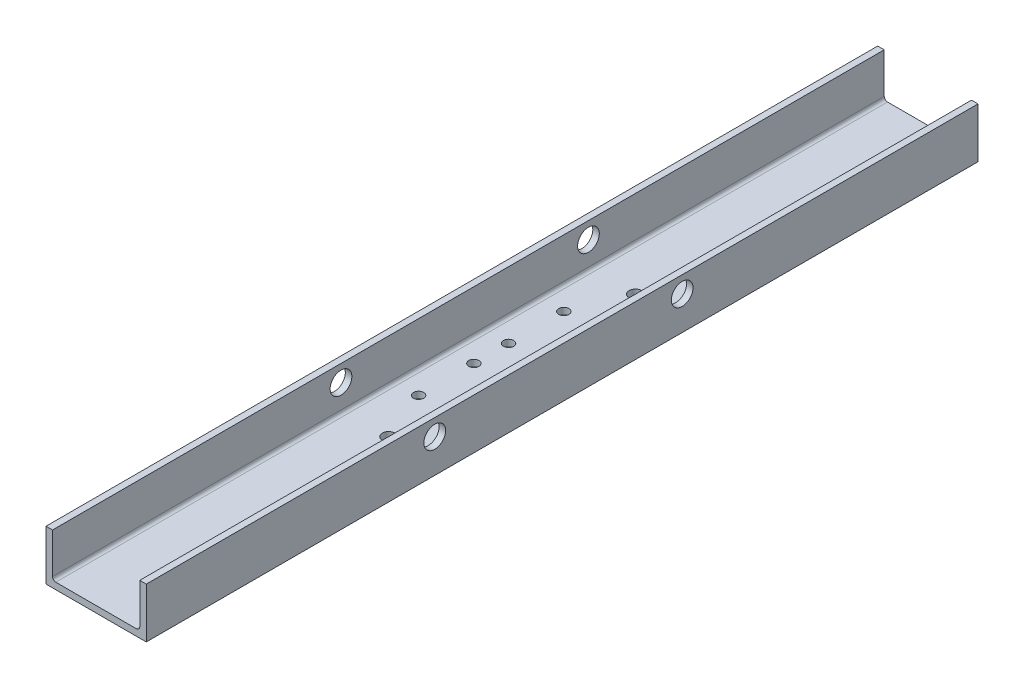
SolidWorks part; units mm, degrees
ref_plane "Front Plane" through (0, 0, 0) normal (0, 0, 1) x (1, 0, 0)
ref_plane "Top Plane" through (0, 0, 0) normal (0, 1, 0) x (1, 0, 0)
ref_plane "Right Plane" through (0, 0, 0) normal (1, 0, 0) x (0, 0, -1)
sketch "Sketch1" plane through (0, 0, 0) normal (0, 0, 1) x (1, 0, 0)
  line L0 (-25.4, 12.7) -> (-25.4, -12.7) construction
  line L1 (-25.4, -12.7) -> (25.4, -12.7) construction
  line L2 (25.4, -12.7) -> (25.4, 12.7) construction
  line L3 (22.098, -9.398) -> (-22.098, -9.398) construction
  line L4 (-22.098, -9.398) -> (-22.098, 12.7) construction
  line L6 (-22.098, 12.7) -> (-25.4, 12.7) construction
  line L7 (0, -12.7) -> (0, 0) construction
  line L8 (25.4, 12.7) -> (22.098, 12.7) construction
  line L9 (22.098, 12.7) -> (22.098, -9.398) construction
  line L10 (0, -9.398) -> (0, -12.7) construction
  point P4 (0, 0)
  point P11 (25.4, -9.398)
  dimension "Outside Height" = 25.4
  dimension "Outside Width" = 50.8
  dimension "Leg Thickness" = 3.302
  dimension "D1" = 12.7
  dimension "Inside Height" = 22.098
  dimension "Inside Width" = 44.196
  dimension "Base Thickness" = 3.302
sketch "Sketch2" plane through (0, 0, 0) normal (1, 0, 0) x (0, 0, -1)
  line L0 (210.695, 12.7) -> (-210.695, 12.7) construction
  line L1 (0, -9.398) -> (0, 12.7) construction
  point P0 (-159.895, 12.7)
  point P4 (0, 12.7)
  point P6 (159.895, 12.7)
  dimension "D1" = 50.8
  dimension "D2" = 50.8
  dimension "Length" = 421.39
sketch "Sketch3" plane through (0, 0, 0) normal (0, 0, 1) x (1, 0, 0)
  line L6 (-25.4, 12.7) -> (-25.4, -12.7)
  line L7 (-25.4, -12.7) -> (25.4, -12.7)
  line L8 (25.4, -12.7) -> (25.4, 12.7)
  line L9 (25.4, 12.7) -> (22.098, 12.7)
  line L10 (22.098, 12.7) -> (22.098, -9.398)
  line L11 (22.098, -9.398) -> (-22.098, -9.398)
  line L12 (-22.098, -9.398) -> (-22.098, 12.7)
  line L13 (-22.098, 12.7) -> (-25.4, 12.7)
extrude "Boss-Extrude1" add sketch "Sketch3" along normal mid plane 421.39
fillet "Fillet1" radius 1.651 2 edges at (22.098, -9.398, 0) (-22.098, -9.398, 0)
sketch "Sketch4" plane through (0, -9.398, 0) normal (0, 1, 0) x (1, 0, 0)
  line L0 (0, 210.695) -> (0, -210.695) construction
  line L1 (20.447, 210.695) -> (-20.447, 210.695) construction
  line L2 (20.447, -210.695) -> (-20.447, -210.695) construction
  line L3 (-23.5304, 0) -> (23.5304, 0) construction
  circle A0 centre (-10.5304, 8.79) radius 2.585
  circle A1 centre (10.4696, 8.79) radius 2.585
  circle A2 centre (-10.5304, 36.79) radius 2.585
  circle A3 centre (10.4696, 36.79) radius 2.585
  circle A4 centre (-10.5304, -36.79) radius 2.585
  circle A5 centre (10.4696, -36.79) radius 2.585
  circle A6 centre (10.4696, -8.79) radius 2.585
  circle A7 centre (-10.5304, -8.79) radius 2.585
  point P24 (0, 0)
  point P26 (0, 0)
  dimension "D1" = 5.17
  dimension "D2" = 5.17
  dimension "D3" = 28
  dimension "D4" = 8.79
  dimension "D5" = 8.79
  dimension "D6" = 28
extrude "Cut-Extrude1" cut sketch "Sketch4" against normal blind 10
sketch "Sketch5" plane through (0, -9.398, 0) normal (0, 1, 0) x (1, 0, 0)
  circle A0 centre (0, 62.5214) radius 3.18
  circle A2 centre (0, -62.52) radius 3.18
  circle A3 centre (-10.5304, -8.79) radius 2.585 construction
  dimension "D1" = 53.73
extrude "Cut-Extrude2" cut sketch "Sketch5" against normal through all
sketch "Sketch6" plane through (22.098, 0, 0) normal (-1, 0, 0) x (0, 0, 1)
  circle A0 centre (64.5436, 4.265) radius 5.5
  circle A1 centre (62.52, 14.351) radius 10.287 construction
  circle A2 centre (-60.8275, 4.2649) radius 5.5
  dimension "D1" = 125.3711
extrude "Cut-Extrude3" cut sketch "Sketch6" against normal through all
sketch "Sketch7" plane through (-25.4, 0, 0) normal (-1, 0, 0) x (0, 0, 1)
  circle A0 centre (64.5436, 4.265) radius 5.5 construction
  circle A1 centre (-60.8275, 4.2649) radius 5.5 construction
  circle A2 centre (64.5436, 4.265) radius 5.5
  circle A3 centre (-60.8275, 4.2649) radius 5.5
extrude "Cut-Extrude4" cut sketch "Sketch7" against normal through all
equation "\"D1@Boss-Extrude1\"=\"Length@Sketch2\""
equation "\"D2@Sketch2\"=\"D1@Sketch2\""
equation "\"D1@Sketch1\"=\"Outside Height@Sketch1\"/2"
equation "\"D1@Fillet1\"=\"Leg Thickness@Sketch1\"*.5"
equation "\"D1@Sketch2\"=\"Outside Width@Sketch1\"*1"
